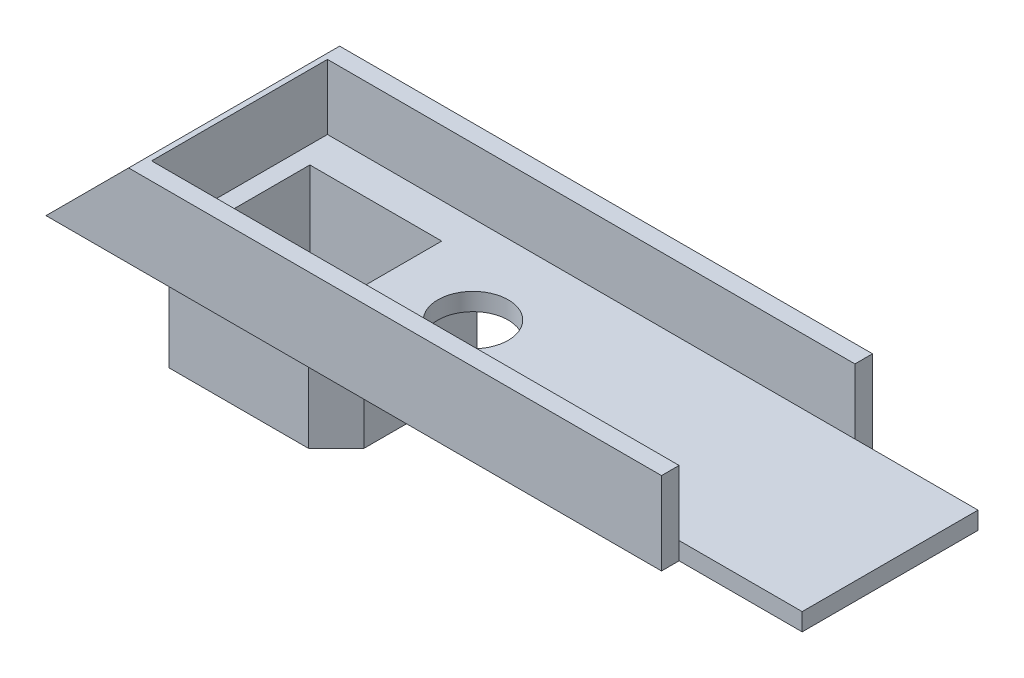
SolidWorks part; units mm, degrees
ref_plane "前视基准面" through (0, 0, 0) normal (0, 0, 1) x (1, 0, 0)
ref_plane "上视基准面" through (0, 0, 0) normal (0, 1, 0) x (1, 0, 0)
ref_plane "右视基准面" through (0, 0, 0) normal (1, 0, 0) x (0, 0, -1)
sketch "草图1" plane through (0, 0, 0) normal (0, 1, 0) x (1, 0, 0)
  line L0 (-12.5242, -6.4845) -> (-12.5242, -12.4845)
  line L1 (-13.5242, -4.4845) -> (-4.0242, -4.4845) construction
  line L2 (-13.5242, -4.4845) -> (-13.5242, -14.4845) construction
  line L3 (-13.5242, -14.4845) -> (-4.0242, -14.4845) construction
  line L4 (23.4758, -4.4845) -> (23.4758, -14.4845)
  line L5 (-12.5242, -12.4845) -> (-6.0242, -12.4845)
  line L6 (-5.0242, -11.4845) -> (-5.0242, -6.4845)
  line L7 (-5.0242, -6.4845) -> (-12.5242, -6.4845)
  line L8 (-6.0242, -12.4845) -> (-5.0242, -11.4845)
  line L9 (-53.0418, -9.4845) -> (30.158, -9.4845) construction
  line L13 (3.9758, -4.4845) -> (23.4758, -4.4845) construction
  line L17 (3.9758, -14.4845) -> (23.4758, -14.4845) construction
  line L18 (-4.0242, -3.4845) -> (-14.5242, -3.4845)
  line L19 (-14.5242, -3.4845) -> (-14.5242, -15.4845)
  line L20 (-14.5242, -15.4845) -> (-4.0242, -15.4845)
  line L21 (2.9758, -3.4845) -> (16.4758, -3.4845)
  line L22 (16.4758, -3.4845) -> (16.4758, -4.4845)
  line L23 (16.4758, -15.4845) -> (16.4758, -14.4845)
  line L24 (2.9758, -15.4845) -> (16.4758, -15.4845)
  line L25 (16.4758, -4.4845) -> (23.4758, -4.4845)
  line L26 (23.4758, -14.4845) -> (16.4758, -14.4845)
  line L27 (-4.0242, -15.4845) -> (2.9758, -15.4845)
  line L28 (-4.0242, -3.4845) -> (2.9758, -3.4845)
  point P12 (23.4758, -9.4845)
  dimension "D1" = 37
  dimension "D2" = 10
  dimension "D3" = 6
  dimension "D4" = 2
  dimension "D5" = 7.5
  dimension "D6" = 135
  dimension "D7" = 1
  dimension "D8" = 5
  dimension "D10" = 1
  dimension "D11" = 1
  dimension "D12" = 1
  dimension "D14" = 12.5
extrude "凸台-拉伸1" add sketch "草图1" along normal blind 1
sketch "草图2" plane through (0, 0, 0) normal (0, -1, 0) x (1, 0, 0)
  line L0 (-12.5242, 12.4845) -> (-6.0242, 12.4845)
  line L1 (-12.5242, 12.4845) -> (-6.0242, 12.4845) construction
  line L2 (-6.0242, 12.4845) -> (-5.0242, 11.4845) construction
  line L3 (-6.0242, 12.4845) -> (-5.0242, 11.4845)
  line L4 (-5.0242, 11.4845) -> (-5.0242, 6.4845)
  line L5 (-5.0242, 6.4845) -> (-12.5242, 6.4845)
  line L6 (-12.5242, 6.4845) -> (-12.5242, 12.4845)
  line L7 (-13.5242, 5.4845) -> (-13.5242, 13.4845)
  line L8 (-13.5242, 13.4845) -> (-5.61, 13.4845)
  line L9 (-5.61, 13.4845) -> (-4.0242, 11.8987)
  line L10 (-4.0242, 11.8987) -> (-4.0242, 5.4845)
  line L11 (-4.0242, 5.4845) -> (-13.5242, 5.4845)
  dimension "D1" = 1
extrude "凸台-拉伸2" add sketch "草图2" along normal blind 6
sketch "草图3" plane through (0, 1, 0) normal (0, 1, 0) x (1, 0, 0)
  line L1 (-18.2722, -9.4845) -> (28.1646, -9.4845) construction
  line L2 (-14.5242, -3.4845) -> (-14.5242, -15.4845) construction
  circle A0 centre (-0.2442, -9.4845) radius 2
  dimension "D1" = 4
  dimension "D2" = 14.28
extrude "切除-拉伸1" cut sketch "草图3" against normal blind 1
sketch "草图4" plane through (0, 1, 0) normal (0, 1, 0) x (1, 0, 0)
  line L0 (-14.5242, -3.4845) -> (16.4758, -3.4845)
  line L1 (16.4758, -3.4845) -> (16.4758, -4.4845)
  line L2 (16.4758, -4.4845) -> (-13.5242, -4.4845)
  line L3 (-14.5242, -3.4845) -> (-14.5242, -15.4845)
  line L4 (-14.5242, -15.4845) -> (16.4758, -15.4845)
  line L5 (16.4758, -15.4845) -> (16.4758, -14.4845)
  line L6 (16.4758, -14.4845) -> (-13.5242, -14.4845)
  line L7 (-13.5242, -14.4845) -> (-13.5242, -4.4845)
  dimension "D1" = 1
extrude "凸台-拉伸3" add sketch "草图4" along normal blind 3.7
sketch "草图5" plane through (0, 4.7, 0) normal (0, 1, 0) x (1, 0, 0)
  line L0 (-14.5242, -3.4845) -> (-14.5242, -15.4845)
  line L1 (-14.5242, -15.4845) -> (-4.0242, -15.4845)
  line L2 (-14.5242, -15.4845) -> (16.4758, -15.4845) construction
  line L3 (-14.5242, -3.4845) -> (-4.0242, -3.4845)
  line L4 (16.4758, -3.4845) -> (-14.5242, -3.4845) construction
  line L5 (-4.0242, -3.4845) -> (-4.0242, -10.3045)
  line L6 (-6.7242, -10.3045) -> (-6.7242, -12.8045)
  line L7 (-6.7242, -12.8045) -> (-4.0242, -12.8045)
  line L9 (-4.0242, -10.3045) -> (-6.7242, -10.3045)
  line L10 (-4.0242, -12.8045) -> (-4.0242, -15.4845)
  dimension "D1" = 7.8
  dimension "D2" = 2.68
  dimension "D3" = 2.5
  dimension "D4" = 2.7
sketch "草图6" plane through (0, 1, 0) normal (0, 1, 0) x (1, 0, 0)
  line L0 (-14.5242, -3.4845) -> (-14.5242, -15.4845) construction
  line L2 (-17.6881, -9.4845) -> (25.119, -9.4845) construction
  point P0 (-14.5242, -9.4845)
sketch "草图7" plane through (0, 0, 15.4845) normal (0, 0, 1) x (1, 0, 0)
  line L0 (-14.5242, 0) -> (-14.5242, 4.7)
  line L1 (-14.5242, 4.7) -> (-19.2242, 0)
  line L3 (-19.2242, 0) -> (-14.5242, 0)
  dimension "D1" = 45
extrude "凸台-拉伸4" add sketch "草图7" against normal blind 12
sketch "草图8" plane through (0, 0, 15.4845) normal (0, 0, 1) x (1, 0, 0)
  line L0 (-14.5242, 4.7) -> (-19.2242, 0)
  line L1 (-19.2242, 0) -> (-18.5312, 0)
  line L2 (-19.2242, 0) -> (16.4758, 0) construction
  line L3 (-18.5312, 0) -> (-13.8312, 4.7)
  line L4 (-14.5242, 4.7) -> (-4.0242, 4.7) construction
  line L5 (-13.8312, 4.7) -> (-14.5242, 4.7)
  dimension "D1" = 0.49
extrude "切除-拉伸2" cut sketch "草图8" against normal blind 12
